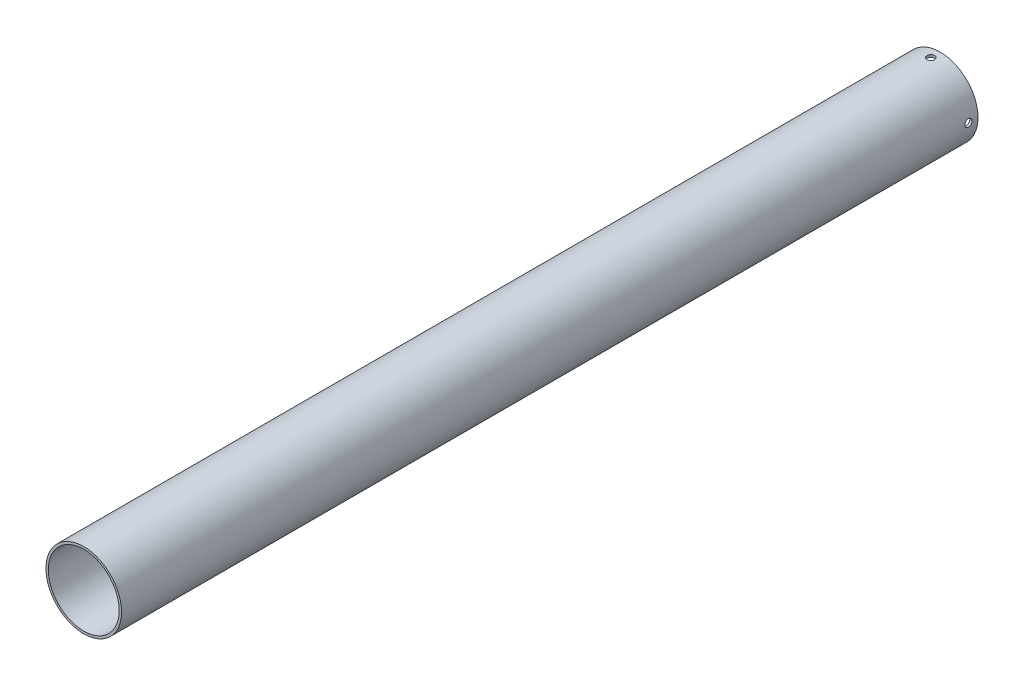
SolidWorks part; units mm, degrees
material "PC High Viscosity"
ref_plane "Front Plane" through (0, 0, 0) normal (0, 0, 1) x (1, 0, 0)
ref_plane "Top Plane" through (0, 0, 0) normal (0, 1, 0) x (1, 0, 0)
ref_plane "Right Plane" through (0, 0, 0) normal (1, 0, 0) x (0, 0, -1)
sketch "Sketch1" plane through (0, 0, 0) normal (0, 0, 1) x (1, 0, 0)
  circle A0 centre (0, 0) radius 23.8125
  circle A1 centre (0, 0) radius 25.4
  dimension "D1" = 50.8
  dimension "D2" = 47.625
extrude "Boss-Extrude1" add sketch "Sketch1" along normal mid plane 575.213
sketch "Sketch2" plane through (0, 0, 0) normal (1, 0, 0) x (0, 0, -1)
  line L0 (287.6065, -25.4) -> (287.6065, 25.4) construction
  circle A0 centre (281.2565, 0) radius 2.4892
  dimension "D1" = 6.35
  dimension "D2" = 4.9784
extrude "Cut-Extrude1" cut sketch "Sketch2" against normal through all both and the other way through all
sketch "Sketch3" plane through (0, 0, 0) normal (0, 1, 0) x (1, 0, 0)
  line L0 (25.4, 287.6065) -> (-25.4, 287.6065) construction
  circle A0 centre (0, 281.2565) radius 2.4892
  dimension "D1" = 4.9784
  dimension "D2" = 6.35
extrude "Cut-Extrude2" cut sketch "Sketch3" against normal through all both and the other way through all
equation "\"D1@Boss-Extrude1\"=21.125in+3.625mm"
